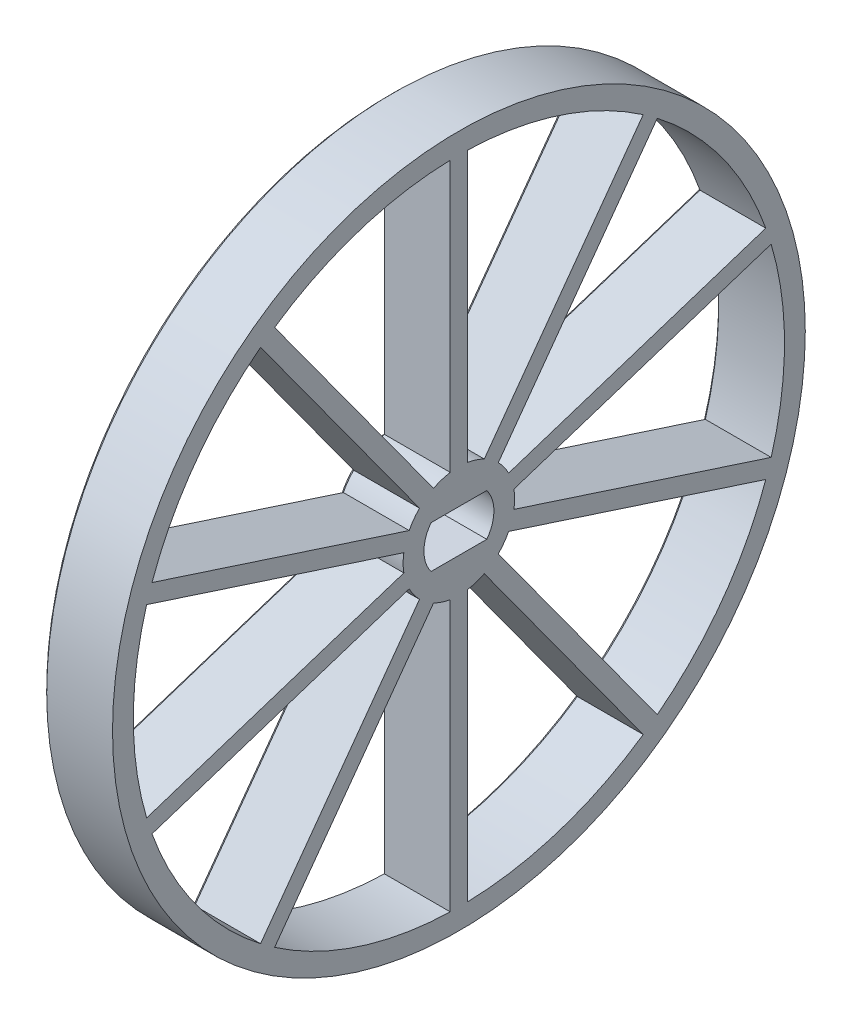
SolidWorks part; units mm, degrees
ref_plane "Front Plane" through (0, 0, 0) normal (0, 0, 1) x (1, 0, 0)
ref_plane "Top Plane" through (0, 0, 0) normal (0, 1, 0) x (1, 0, 0)
ref_plane "Right Plane" through (0, 0, 0) normal (1, 0, 0) x (0, 0, -1)
sketch "Sketch1" plane through (0, 0, 0) normal (1, 0, 0) x (0, 0, -1)
  line L0 (0, 0) -> (0, 27.6652) construction
  line L1 (-2.65, -1.525) -> (2.65, -1.525)
  line L2 (-2.65, -1.525) -> (-2.65, 1.525)
  line L3 (-2.65, 1.525) -> (2.65, 1.525)
  line L4 (2.65, -1.525) -> (2.65, 1.525)
  line L5 (-2.65, -1.525) -> (2.65, 1.525) construction
  line L6 (-2.65, 1.525) -> (2.65, -1.525) construction
  line L8 (-0.625, 3.8326) -> (0.625, 3.8326)
  line L9 (-0.625, 3.8326) -> (-0.625, 23.8326)
  line L10 (-0.625, 23.8326) -> (0.625, 23.8326)
  line L11 (0.625, 3.8326) -> (0.625, 23.8326)
  line L12 (-0.625, 3.8326) -> (0.625, 23.8326) construction
  line L13 (-0.625, 23.8326) -> (0.625, 3.8326) construction
  line L57 (1.7471, 3.468) -> (13.5028, 19.6484)
  line L58 (1.7471, 3.468) -> (2.7584, 2.7333)
  line L59 (2.7584, 2.7333) -> (14.5141, 18.9136)
  line L60 (13.5028, 19.6484) -> (14.5141, 18.9136)
  line L61 (3.4519, 1.7788) -> (22.473, 7.9591)
  line L62 (3.4519, 1.7788) -> (3.8382, 0.5899)
  line L63 (3.8382, 0.5899) -> (22.8593, 6.7703)
  line L64 (22.473, 7.9591) -> (22.8593, 6.7703)
  line L65 (3.8382, -0.5899) -> (22.8593, -6.7703)
  line L66 (3.8382, -0.5899) -> (3.4519, -1.7788)
  line L67 (3.4519, -1.7788) -> (22.473, -7.9591)
  line L68 (22.8593, -6.7703) -> (22.473, -7.9591)
  line L69 (2.7584, -2.7333) -> (14.5141, -18.9136)
  line L70 (2.7584, -2.7333) -> (1.7471, -3.468)
  line L71 (1.7471, -3.468) -> (13.5028, -19.6484)
  line L72 (14.5141, -18.9136) -> (13.5028, -19.6484)
  line L73 (0.625, -3.8326) -> (0.625, -23.8326)
  line L74 (0.625, -3.8326) -> (-0.625, -3.8326)
  line L75 (-0.625, -3.8326) -> (-0.625, -23.8326)
  line L76 (0.625, -23.8326) -> (-0.625, -23.8326)
  line L77 (-1.7471, -3.468) -> (-13.5028, -19.6484)
  line L78 (-1.7471, -3.468) -> (-2.7584, -2.7333)
  line L79 (-2.7584, -2.7333) -> (-14.5141, -18.9136)
  line L80 (-13.5028, -19.6484) -> (-14.5141, -18.9136)
  line L81 (-3.4519, -1.7788) -> (-22.473, -7.9591)
  line L82 (-3.4519, -1.7788) -> (-3.8382, -0.5899)
  line L83 (-3.8382, -0.5899) -> (-22.8593, -6.7703)
  line L84 (-22.473, -7.9591) -> (-22.8593, -6.7703)
  line L85 (-3.8382, 0.5899) -> (-22.8593, 6.7703)
  line L86 (-3.8382, 0.5899) -> (-3.4519, 1.7788)
  line L87 (-3.4519, 1.7788) -> (-22.473, 7.9591)
  line L88 (-22.8593, 6.7703) -> (-22.473, 7.9591)
  line L89 (-2.7584, 2.7333) -> (-14.5141, 18.9136)
  line L90 (-2.7584, 2.7333) -> (-1.7471, 3.468)
  line L91 (-1.7471, 3.468) -> (-13.5028, 19.6484)
  line L92 (-14.5141, 18.9136) -> (-13.5028, 19.6484)
  circle A0 centre (0, 0) radius 2.525
  circle A1 centre (0, 0) radius 4.025
  circle A2 centre (0, 0) radius 25
  circle A3 centre (0, 0) radius 23.5
  point P10 (0, 13.8326)
  point P54 (0, 0)
  point P63 (0, 0)
  dimension "D1" = 5.05
  dimension "D3" = 1.5
  dimension "D4" = 1.5
  dimension "D5" = 50
  dimension "D2" = 3.05
  dimension "D6" = 1.25
  dimension "D7" = 20
  dimension "D8" = 10
extrude "Boss-Extrude1" add sketch "Sketch1" along normal blind 5 contours A2 A3 L61 L64 L63 L65 L68 L67 L69 L72 L71 L73 L76 L75 L77 L80 L79 L81 L84 L83 L85 L88 L87 L89 L92 L91 L9 L10 L11 L57 L60 L59 | A3 L59 L60 L57 | L59 A3 L57 A1 | A3 L11 L10 L9 | L11 A3 L9 A1 | L91 A3 L89 A1 | A3 L91 L92 L89 | L87 A3 L85 A1 | A3 L87 L88 L85 | A3 L83 L84 L81 | L83 A3 L81 A1 | A3 L79 L80 L77 | L79 A3 L77 A1 | A3 L75 L76 L73 | L75 A3 L73 A1 | A3 L71 L72 L69 | L71 A3 L69 A1 | A3 L67 L68 L65 | L67 A3 L65 A1 | A3 L63 L64 L61 | L63 A3 L61 A1 | L11 A1 L9 L8 | L59 A1 L57 L58 | L63 A1 L61 L62 | L67 A1 L65 L66 | L71 A1 L69 L70 | L91 A1 L89 L90 | L87 A1 L85 L86 | L83 A1 L81 L82 | L79 A1 L77 L78 | L75 A1 L73 L74 | L61 A1 L59 L58 L57 L11 L8 L9 L91 L90 L89 L87 L86 L85 L83 L82 L81 L79 L78 L77 L75 L74 L73 L71 L70 L69 L67 L66 L65 L63 L62 A0 L3 L4 L1 L2 | A0 L3 L2 L1 | L3 A0 | L1 A0 | A0 L1 L4 L3 region at (0, 0, 2.6188) region at (0, -1.9327, 0) region at (0, -0.8143, -2.423) region at (0, 1.9327, 0) region at (0, 3.9213, 0) region at (0, 3.7195, 0) region at (0, 13.753, 0) region at (0, 23.6649, 0) region at (0, 11.1264, 8.0838) region at (0, 3.1724, 2.3049) region at (0, 3.1724, -2.3049) region at (0, 11.1264, -8.0838) region at (0, 19.1453, 13.9099) region at (0, 19.1453, -13.9099) region at (0, 4.2499, 13.0799) region at (0, 1.2117, 3.7294) region at (0, 1.2117, -3.7294) region at (0, 4.2499, -13.0799) region at (0, 7.3129, 22.5067) region at (0, 7.3129, -22.5067) region at (0, -4.2499, 13.0799) region at (0, -1.2117, 3.7294) region at (0, -7.3129, 22.5067) region at (0, -1.2117, -3.7294) region at (0, -4.2499, -13.0799) region at (0, -11.1264, 8.0838) region at (0, -3.1724, 2.3049) region at (0, -7.3129, -22.5067) region at (0, -19.1453, 13.9099) region at (0, -3.1724, -2.3049) region at (0, -11.1264, -8.0838) region at (0, -13.753, 0) region at (0, -3.9213, 0) region at (0, -19.1453, -13.9099) region at (0, -23.6649, 0) region at (0, 0, 24.2929)
chamfer "Chamfer2" distance 0.25 angle 45 45 edges at (0, 0, -25) (0, 13.7339, -0.625) (0, 22.3498, -7.2619) (0, 11.4784, -7.567) (0, 3.828, -1.2438) (0, 11.4784, 7.567) (0, 22.3498, 7.2619) (0, 13.7339, 0.625) (0, 3.828, 1.2438) (0, 4.8384, 12.8686) (0, 13.813, 19.0119) (0, 10.7436, 8.5782) (0, 2.3658, 3.2563) (0, -3.6496, 13.2549) (0, 0, 23.5) (0, 3.6496, 13.2549) (0, 0, 4.025) (0, -10.7436, 8.5782) (0, -13.813, 19.0119) (0, -4.8384, 12.8686) (0, -2.3658, 3.2563) (0, -13.7339, 0.625) (0, -22.3498, 7.2619) (0, -11.4784, 7.567) (0, -3.828, 1.2438) (0, -11.4784, -7.567) (0, -22.3498, -7.2619) (0, -13.7339, -0.625) (0, -3.828, -1.2438) (0, -4.8384, -12.8686) (0, -13.813, -19.0119) (0, -10.7436, -8.5782) (0, -2.3658, -3.2563) (0, 2.3658, -3.2563) (0, 10.7436, -8.5782) (0, 13.813, -19.0119) (0, 4.8384, -12.8686) (0, 3.6496, -13.2549) (0, 0, -23.5) (0, -3.6496, -13.2549) (0, 0, -4.025) (0, 1.525, 0) (0, 0, -2.525) (0, -1.525, 0) (0, 0, 2.525)
